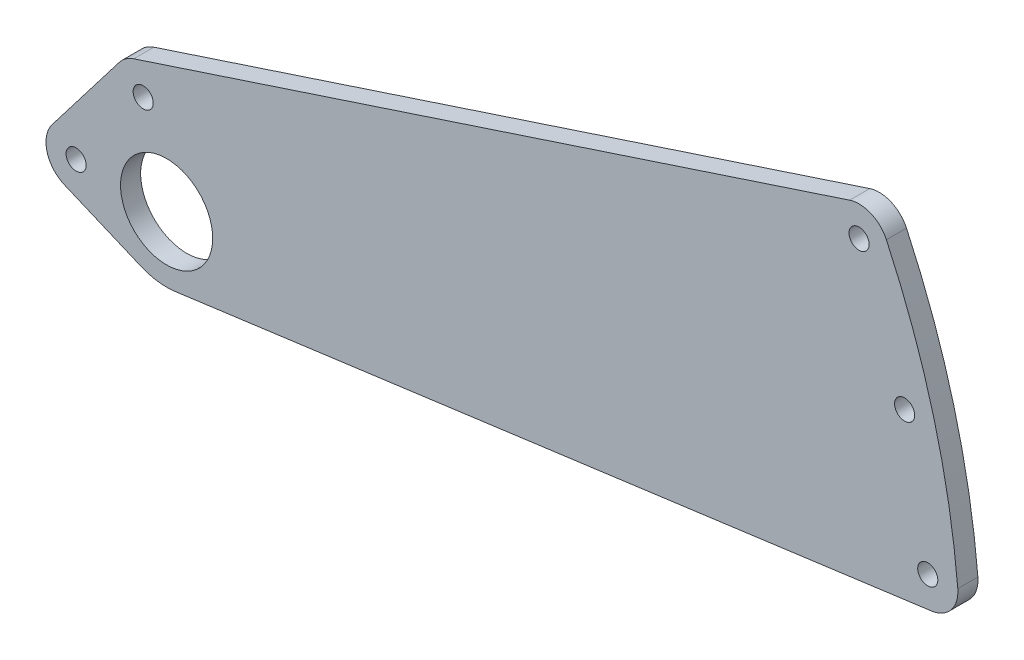
SolidWorks part; units mm, degrees
material "6061-T6 (SS)"
ref_plane "Front Plane" through (0, 0, 0) normal (0, 0, 1) x (1, 0, 0)
ref_plane "Top Plane" through (0, 0, 0) normal (0, 1, 0) x (1, 0, 0)
ref_plane "Right Plane" through (0, 0, 0) normal (1, 0, 0) x (0, 0, -1)
sketch "Sketch1" plane through (0, 0, 0) normal (0, 0, 1) x (1, 0, 0)
  line L0 (0, 0) -> (-28.575, 0) construction
  line L1 (0, 0) -> (-7.3958, 27.6013) construction
  line L2 (0, 0) -> (240.3818, 21.0307) construction
  line L3 (0, 0) -> (39.1426, 0) construction
  line L4 (0, 0) -> (240.3818, 21.0307) construction
  line L5 (0, 0) -> (233.0779, 62.453) construction
  line L6 (-36.1317, 5.7985) -> (-14.9524, 33.3998)
  line L7 (-32.2792, -8.7752) -> (-8.0257, -19.013)
  line L8 (-10.3723, 36.6493) -> (215.7155, 111.0258)
  line L9 (2.7436, -20.4543) -> (241.648, 11.5902)
  circle A0 centre (0, 0) radius 14.5542
  circle A1 centre (-28.575, 0) radius 3.175
  circle A2 centre (-7.3958, 27.6013) radius 3.175
  circle A3 centre (240.3818, 21.0307) radius 3.175
  circle A4 centre (233.0779, 62.453) radius 3.175
  circle A5 centre (218.6921, 101.9778) radius 3.175
  arc A6 (2.7436, -20.4543) -> (-8.0257, -19.013) centre (0, 0) cw
  arc A7 (-32.2792, -8.7752) -> (-36.1317, 5.7985) centre (-28.575, 0) cw
  arc A8 (-10.3723, 36.6493) -> (-14.9524, 33.3998) centre (-7.3958, 27.6013) ccw
  arc A9 (227.3247, 106.0032) -> (215.7155, 111.0258) centre (218.6921, 101.9778) ccw
  arc A10 (227.3247, 106.0032) -> (249.8705, 21.8608) centre (0, 0) cw
  arc A11 (249.8705, 21.8608) -> (241.648, 11.5902) centre (240.3818, 21.0307) cw
  dimension "D1" = 29.1084
  dimension "D3" = 6.35
  dimension "D6" = 6.35
  dimension "D9" = 6.35
  dimension "D12" = 9.525
  dimension "D13" = 9.525
  dimension "D14" = 20.6375
  dimension "D15" = 9.525
  dimension "D2" = 28.575
  dimension "D4" = 75
  dimension "D5" = 28.575
  dimension "D7" = 5
  dimension "D8" = 241.3
  dimension "D11" = 10
  dimension "D10" = 3
extrude "Boss-Extrude1" add sketch "Sketch1" along normal blind 6.35
